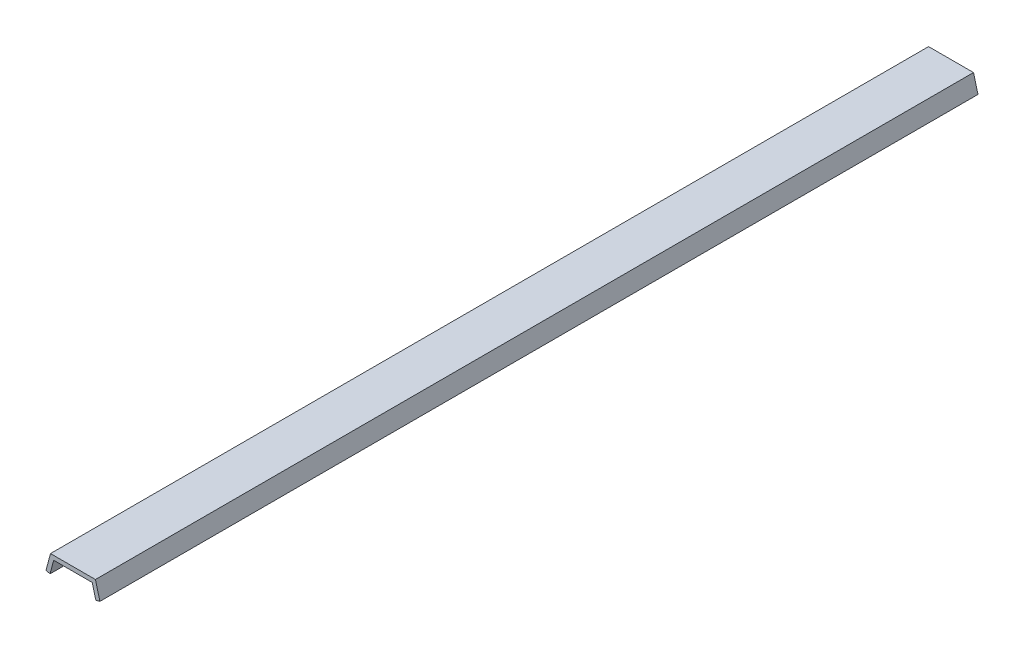
SolidWorks part; units mm, degrees
material "ABS PC"
ref_plane "Front Plane" through (0, 0, 0) normal (0, 0, 1) x (1, 0, 0)
ref_plane "Top Plane" through (0, 0, 0) normal (0, 1, 0) x (1, 0, 0)
ref_plane "Right Plane" through (0, 0, 0) normal (1, 0, 0) x (0, 0, -1)
sketch "Sketch2" plane through (0, 0, 0) normal (0, 0, 1) x (1, 0, 0)
  line L0 (0, 0) -> (0, 4) construction
  line L1 (5.375, 4) -> (-5.375, 4)
  line L2 (-5.375, 4) -> (-6.4468, 0)
  line L3 (-6.4468, 0) -> (0, 0) construction
  line L4 (5.375, 4) -> (6.4468, 0)
  dimension "D1" = 10.75
  dimension "D2" = 4
  dimension "D3" = 75
extrude "Extrude-Thin1" add sketch "Sketch2" along normal mid plane 210 thin thin type one direction wall 1
